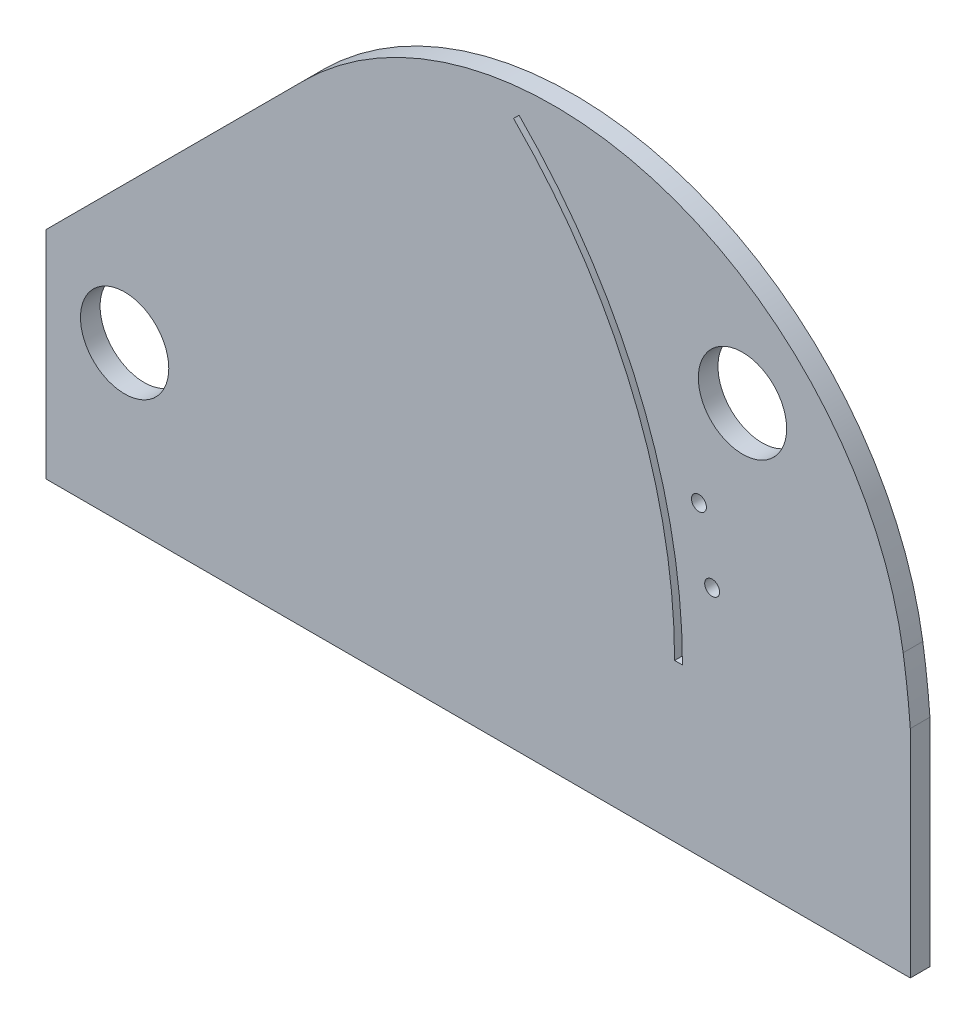
SolidWorks part; units mm, degrees
ref_plane "Front Plane" through (0, 0, 0) normal (0, 0, 1) x (1, 0, 0)
ref_plane "Top Plane" through (0, 0, 0) normal (0, 1, 0) x (1, 0, 0)
ref_plane "Right Plane" through (0, 0, 0) normal (1, 0, 0) x (0, 0, -1)
sketch "Sketch1" plane through (0, 0, 0) normal (0, 0, 1) x (1, 0, 0)
  line L0 (-25.4, -50.8) -> (254, -50.8)
  line L2 (-25.4, 19.05) -> (-25.4, -50.8)
  line L3 (0, 0) -> (50.8, 0) construction
  line L4 (254, -50.8) -> (254, 19.05)
  line L7 (156.508, 200.958) -> (-25.4, 19.05)
  line L8 (-25.4, 19.05) -> (254, 19.05) construction
  line L9 (-25.4, 276.3068) -> (-25.4, 19.05) construction
  circle A1 centre (0, 0) radius 14.2748
  arc A6 (-25.4, 276.3068) -> (156.508, 200.958) centre (-25.4, 19.05) cw construction
  arc A8 (254, 19.05) -> (156.508, 200.958) centre (0, 0) ccw
  dimension "D1" = 50.8
  dimension "D2" = 28.5496
  dimension "D6" = 69.85
  dimension "D3" = 25.4
  dimension "D4" = 50.8
  dimension "D5" = 279.4
  dimension "D8" = 45
extrude "Boss-Extrude1" add sketch "Sketch1" along normal blind 6.35
sketch "Sketch2" plane through (0, 0, 6.35) normal (0, 0, 1) x (1, 0, 0)
  line L2 (127.5196, 127.5196) -> (125.7236, 125.7236)
  line L3 (177.8, 0) -> (180.34, 0)
  line L4 (0, 0) -> (127.5196, 127.5196) construction
  line L5 (180.34, 0) -> (0, 0) construction
  arc A3 (125.7236, 125.7236) -> (177.8, 0) centre (0, 0) cw
  arc A4 (127.5196, 127.5196) -> (180.34, 0) centre (0, 0) cw
  dimension "D1" = 177.8
  dimension "D4" = 180.34
  dimension "D5" = 45
extrude "Cut-Extrude1" cut sketch "Sketch2" against normal through all contours L3 A4 L2 A3
sketch "Sketch3" plane through (0, 0, 6.35) normal (0, 0, 1) x (1, 0, 0)
  line L0 (0, 0) -> (199.7412, 83.0049) construction
  line L1 (0, 0) -> (199.3587, 0) construction
  circle A0 centre (199.7412, 83.0049) radius 14.2748
  dimension "D3" = 28.5496
  dimension "D1" = 216.3016
  dimension "D2" = 22.566
extrude "Cut-Extrude2" cut sketch "Sketch3" against normal through all
sketch "Sketch5" plane through (0, 0, 6.35) normal (0, 0, 1) x (1, 0, 0)
  line L0 (0, 0) -> (210.531, 0) construction
  line L1 (0, 0) -> (189.9408, 26.424) construction
  line L2 (0, 0) -> (185.6617, 48.0154) construction
  circle A2 centre (185.6617, 48.0154) radius 2.413
  circle A3 centre (189.9408, 26.424) radius 2.413
  dimension "D1" = 7.92
  dimension "D4" = 4.826
  dimension "D2" = 6.58
  dimension "D3" = 191.77
extrude "Cut-Extrude3" cut sketch "Sketch5" against normal through all and the other way through all
fillet "Fillet1" radius 114.3 1 edges at (156.508, 200.958, 3.175)
